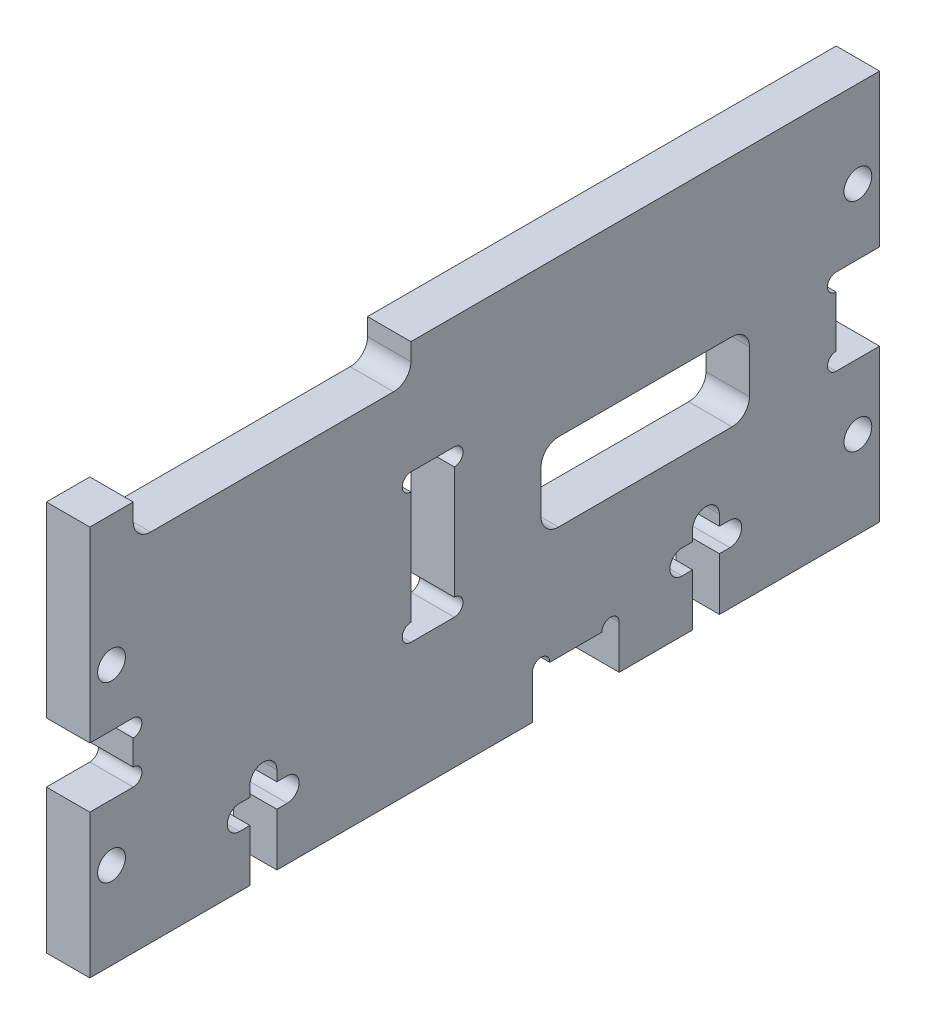
SolidWorks part; units mm, degrees
ref_plane "정면" through (0, 0, 0) normal (0, 0, 1) x (1, 0, 0)
ref_plane "윗면" through (0, 0, 0) normal (0, 1, 0) x (1, 0, 0)
ref_plane "우측면" through (0, 0, 0) normal (1, 0, 0) x (0, 0, -1)
sketch "스케치1" plane through (0, 0, 0) normal (1, 0, 0) x (0, 0, -1)
  line L1 (0, 0) -> (91, 0)
  line L2 (0, 0) -> (0, 45)
  line L3 (0, 45) -> (91, 45)
  line L4 (91, 0) -> (91, 45)
  dimension "D1" = 45
  dimension "D2" = 91
extrude "보스-돌출1" add sketch "스케치1" along normal blind 5
sketch "스케치2" plane through (5, 0, 0) normal (1, 0, 0) x (0, 0, -1)
  line L0 (0, 45) -> (0, 0) construction
  line L1 (0, 41) -> (5, 41)
  line L2 (0, 41) -> (0, 31)
  line L3 (0, 31) -> (5, 31)
  line L4 (5, 41) -> (5, 31)
  line L5 (91, 0) -> (91, 45) construction
  line L6 (0, 19) -> (5, 19)
  line L7 (0, 19) -> (0, 9)
  line L8 (0, 9) -> (5, 9)
  line L9 (5, 19) -> (5, 9)
  line L10 (37, 41) -> (42, 41)
  line L11 (37, 41) -> (37, 31)
  line L12 (37, 31) -> (42, 31)
  line L13 (42, 41) -> (42, 31)
  line L14 (37, 19) -> (42, 19)
  line L15 (37, 19) -> (37, 9)
  line L16 (37, 9) -> (42, 9)
  line L17 (42, 19) -> (42, 9)
  line L18 (86, 41) -> (91, 41)
  line L19 (86, 41) -> (86, 31)
  line L20 (86, 31) -> (91, 31)
  line L21 (91, 41) -> (91, 31)
  line L22 (5, 31) -> (37, 31) construction
  line L23 (86, 19) -> (91, 19)
  line L24 (86, 19) -> (86, 9)
  line L25 (86, 9) -> (91, 9)
  line L26 (91, 19) -> (91, 9)
  line L27 (37, 19) -> (37, 31) construction
  line L28 (5, 19) -> (5, 31) construction
  line L29 (37, 41) -> (5, 41) construction
  line L30 (42, 41) -> (86, 41) construction
  line L31 (86, 31) -> (86, 19) construction
  line L32 (42, 31) -> (42, 19) construction
  line L33 (42, 19) -> (86, 19) construction
  line L34 (86, 31) -> (42, 31) construction
  line L35 (42, 9) -> (86, 9) construction
  line L36 (37, 19) -> (5, 19) construction
  line L37 (5, 9) -> (37, 9) construction
  line L38 (91, 45) -> (0, 45) construction
  dimension "D1" = 5
  dimension "D2" = 5
  dimension "D3" = 5
  dimension "D4" = 10
  dimension "D5" = 10
  dimension "D6" = 12
  dimension "D7" = 4
  dimension "D8" = 32
extrude "컷-돌출1" [suppressed] cut sketch "스케치2" against normal blind 5
sketch "스케치3" [suppressed] plane through (5, 0, 0) normal (1, 0, 0) x (0, 0, -1)
  line L0 (91, 36) -> (86, 36) construction
  line L1 (86, 26) -> (91, 26) construction
  line L2 (91, 14) -> (86, 14) construction
  line L3 (86, 4) -> (91, 4) construction
  line L4 (42, 4) -> (42, 14) construction
  line L5 (37, 14) -> (37, 4) construction
  line L6 (37, 36) -> (37, 26) construction
  line L7 (42, 26) -> (42, 36) construction
  line L9 (5, 14) -> (0, 14) construction
  line L10 (0, 26) -> (5, 26) construction
  line L11 (5, 36) -> (0, 36) construction
  line L12 (0, 4) -> (5, 4) construction
  circle A0 centre (87, 36) radius 1
  circle A1 centre (87, 26) radius 1
  circle A2 centre (87, 14) radius 1
  circle A3 centre (87, 4) radius 1
  circle A4 centre (42, 13) radius 1
  circle A5 centre (37, 13) radius 1
  circle A6 centre (37, 27) radius 1
  circle A7 centre (42, 27) radius 1
  circle A8 centre (42, 35) radius 1
  circle A9 centre (37, 35) radius 1
  circle A10 centre (37, 5) radius 1
  circle A11 centre (42, 5) radius 1
  circle A12 centre (4, 14) radius 1
  circle A13 centre (4, 26) radius 1
  circle A14 centre (4, 36) radius 1
  circle A15 centre (4, 4) radius 1
  dimension "D1" = 2
extrude "컷-돌출2" [suppressed] cut sketch "스케치3" against normal blind 5
sketch "스케치7" plane through (5, 0, 0) normal (1, 0, 0) x (0, 0, -1)
  line L0 (86, 36.55) -> (86, 52) construction
  line L1 (52, 27) -> (76, 27)
  line L2 (52, 27) -> (52, 18)
  line L3 (52, 18) -> (76, 18)
  line L4 (76, 27) -> (76, 18)
  line L5 (42, 34) -> (42, 52) construction
  line L6 (91, 45) -> (0, 45) construction
  line L7 (0, 0) -> (91, 0) construction
  dimension "D1" = 10
  dimension "D2" = 10
  dimension "D3" = 18
  dimension "D4" = 18
extrude "컷-돌출3" cut sketch "스케치7" against normal blind 10
fillet "필렛1" radius 2 4 edges at (2.5, 18, -52) (2.5, 18, -76) (2.5, 27, -76) (2.5, 27, -52)
sketch "스케치8" plane through (5, 0, 0) normal (1, 0, 0) x (0, 0, -1)
  line L0 (91, 45) -> (0, 45) construction
  line L1 (5, 45) -> (37, 45)
  line L2 (5, 45) -> (5, 41)
  line L3 (5, 41) -> (37, 41)
  line L4 (37, 45) -> (37, 41)
  line L5 (5, 31.55) -> (5, 52) construction
  line L6 (37, 34) -> (37, 52) construction
  dimension "D1" = 4
extrude "컷-돌출4" cut sketch "스케치8" against normal blind 10
fillet "필렛2" radius 2 2 edges at (2.5, 41, -37) (2.5, 41, -5)
sketch "스케치9" plane through (0, 0, 0) normal (-1, 0, 0) x (0, 0, 1)
  line L1 (-42, 32) -> (-37, 32)
  line L2 (-42, 32) -> (-42, 15)
  line L3 (-42, 15) -> (-37, 15)
  line L4 (-37, 32) -> (-37, 15)
extrude "컷-돌출5" cut sketch "스케치9" against normal blind 5
sketch "스케치10" plane through (5, 0, 0) normal (1, 0, 0) x (0, 0, -1)
  line L0 (42, 32) -> (42, 15) construction
  line L1 (37, 15) -> (37, 32) construction
  circle A0 centre (42, 31) radius 1
  circle A1 centre (42, 16) radius 1
  circle A2 centre (37, 16) radius 1
  circle A3 centre (37, 31) radius 1
  dimension "D1" = 2
sketch "스케치14" plane through (5, 0, 0) normal (1, 0, 0) x (0, 0, -1)
  line L0 (88.5, 36.55) -> (88.5, 33.585) construction
  line L1 (86, 36.55) -> (91, 36.55) construction
  line L2 (88.5, 11.55) -> (88.5, 8.45) construction
  line L3 (86, 11.55) -> (91, 11.55) construction
  line L4 (86, 8.45) -> (91, 8.45) construction
  line L5 (2.5, 31.55) -> (2.5, 28.45) construction
  line L6 (5, 31.55) -> (0, 31.55) construction
  line L7 (5, 28.45) -> (0, 28.45) construction
  line L8 (2.5, 11.55) -> (2.5, 8.45) construction
  line L9 (5, 11.55) -> (0, 11.55) construction
  line L10 (5, 8.45) -> (0, 8.45) construction
  circle A0 centre (2.5, 10) radius 1.55
  circle A1 centre (2.5, 30) radius 1.55
  circle A2 centre (88.5, 35.0675) radius 1.4825
  circle A3 centre (88.5, 10) radius 1.55
extrude "컷-돌출9" cut sketch "스케치14" against normal blind 10
extrude "컷-돌출6" cut sketch "스케치10" against normal blind 10
sketch "스케치12" plane through (5, 0, 0) normal (1, 0, 0) x (0, 0, -1)
  line L0 (88.5, 35) -> (88.5, 10) construction
  line L1 (2.5, 30) -> (2.5, 10) construction
  line L2 (91, 0) -> (91, 45) construction
  line L3 (91, 45) -> (37, 45) construction
  line L4 (0, 45) -> (0, 0) construction
  line L5 (0, 0) -> (91, 0) construction
  circle A0 centre (2.5, 30) radius 1.6
  circle A1 centre (2.5, 10) radius 1.6
  circle A2 centre (88.5, 35) radius 1.6
  circle A3 centre (88.5, 10) radius 1.6
  dimension "D3" = 3.2
  dimension "D1" = 2.5
  dimension "D2" = 25
  dimension "D4" = 10
  dimension "D5" = 2.5
  dimension "D6" = 20
  dimension "D7" = 10
extrude "컷-돌출7" cut sketch "스케치12" against normal blind 10
sketch "스케치13" plane through (5, 0, 0) normal (1, 0, 0) x (0, 0, -1)
  line L0 (18.45, 0) -> (18.45, 6)
  line L1 (18.45, 0) -> (21.55, 0)
  line L2 (21.55, 0) -> (21.55, 6.0651)
  line L3 (18.45, 10) -> (21.55, 10) construction
  line L4 (21.55, 8.7999) -> (21.55, 10)
  line L5 (18.45, 6) -> (17.2502, 6)
  line L6 (17.2502, 6) -> (17.2325, 8.7999) construction
  line L7 (17.2325, 8.7999) -> (18.45, 8.7999)
  line L8 (21.55, 8.7999) -> (22.7498, 8.7999)
  line L9 (22.7498, 8.7999) -> (22.7498, 6.0651) construction
  line L10 (18.45, 8.7999) -> (18.45, 10)
  line L11 (22.7498, 6.0651) -> (21.55, 6.0651)
  line L12 (18.45, 6) -> (21.55, 6.0651) construction
  line L13 (18.45, 8.7999) -> (21.55, 8.7999) construction
  line L14 (21.55, 6.0651) -> (21.55, 8.7999) construction
  line L15 (18.45, 8.7999) -> (18.45, 6) construction
  line L16 (20, 10) -> (20, 16.1272) construction
  line L17 (0, 45) -> (0, 0) construction
  line L18 (72.55, 0) -> (72.55, 6.0651)
  line L19 (69.45, 10) -> (72.55, 10) construction
  line L20 (68.2502, 6) -> (68.2325, 8.7999) construction
  line L21 (72.55, 6.0651) -> (72.55, 8.7999) construction
  line L22 (69.45, 0) -> (72.55, 0)
  line L23 (68.2325, 8.7999) -> (69.45, 8.7999)
  line L24 (69.45, 0) -> (69.45, 6)
  line L25 (73.7498, 8.7999) -> (73.7498, 6.0651) construction
  line L26 (69.45, 6) -> (68.2502, 6)
  line L27 (69.45, 8.7999) -> (69.45, 6) construction
  line L28 (72.55, 8.7999) -> (72.55, 10)
  line L29 (69.45, 6) -> (72.55, 6.0651) construction
  line L30 (69.45, 8.7999) -> (72.55, 8.7999) construction
  line L31 (72.55, 8.7999) -> (73.7498, 8.7999)
  line L32 (69.45, 8.7999) -> (69.45, 10)
  line L33 (71, 10) -> (71, 16.1272) construction
  line L34 (73.7498, 6.0651) -> (72.55, 6.0651)
  line L35 (91, 0) -> (91, 45) construction
  arc A0 (17.2325, 8.7999) -> (17.2502, 6) centre (17.2414, 7.4) ccw
  arc A1 (22.7498, 6.0651) -> (22.7498, 8.7999) centre (22.7498, 7.4325) ccw
  arc A2 (21.55, 10) -> (18.45, 10) centre (20, 10) ccw
  arc A3 (72.55, 10) -> (69.45, 10) centre (71, 10) ccw
  arc A4 (68.2325, 8.7999) -> (68.2502, 6) centre (68.2414, 7.4) ccw
  arc A5 (73.7498, 6.0651) -> (73.7498, 8.7999) centre (73.7498, 7.4325) ccw
  dimension "D1" = 3.1
  dimension "D2" = 10
  dimension "D3" = 5.5
  dimension "D4" = 2.8
  dimension "D5" = 20
  dimension "D6" = 6
  dimension "D7" = 3.1
  dimension "D8" = 10
  dimension "D9" = 5.5
  dimension "D10" = 2.8
  dimension "D11" = 6
  dimension "D12" = 20
extrude "컷-돌출8" cut sketch "스케치13" against normal blind 10
sketch "스케치15" plane through (5, 0, 0) normal (1, 0, 0) x (0, 0, -1)
  line L0 (21.55, 0) -> (69.45, 0) construction
  line L1 (51, 5) -> (61, 5)
  line L2 (51, 5) -> (51, 0)
  line L3 (51, 0) -> (61, 0)
  line L4 (61, 5) -> (61, 0)
  line L5 (61, 5) -> (61, 0) construction
extrude "컷-돌출10" cut sketch "스케치15" against normal blind 10
sketch "스케치19" plane through (0, 0, 0) normal (-1, 0, 0) x (0, 0, 1)
  line L0 (0, 45) -> (0, 0) construction
  line L1 (-5, 23.45) -> (0, 23.45)
  line L2 (-5, 23.45) -> (-5, 16.55)
  line L3 (-5, 16.55) -> (0, 16.55)
  line L4 (0, 23.45) -> (0, 16.55)
  line L5 (-5, 16.55) -> (0, 16.55) construction
  line L6 (-86, 17.55) -> (-91, 17.55) construction
  line L7 (-86, 27.45) -> (-91, 27.45)
  line L8 (-86, 27.45) -> (-86, 17.55)
  line L9 (-86, 17.55) -> (-91, 17.55)
  line L10 (-91, 27.45) -> (-91, 17.55)
  line L11 (-91, 0) -> (-91, 45) construction
extrude "컷-돌출14" cut sketch "스케치19" against normal blind 5
sketch "스케치16" plane through (0, 0, 0) normal (-1, 0, 0) x (0, 0, 1)
  line L0 (-51, 5) -> (-61, 5) construction
  line L1 (-86, 17.55) -> (-86, 27.45) construction
  line L2 (-5, 23.45) -> (-5, 16.55) construction
  circle A0 centre (-60, 5) radius 1
  circle A1 centre (-52, 5) radius 1
  circle A2 centre (-86, 26.45) radius 1
  circle A3 centre (-86, 18.55) radius 1
  circle A4 centre (-5, 22.45) radius 1
  circle A5 centre (-5, 17.55) radius 1
  dimension "D1" = 2
extrude "컷-돌출11" cut sketch "스케치16" against normal blind 10
